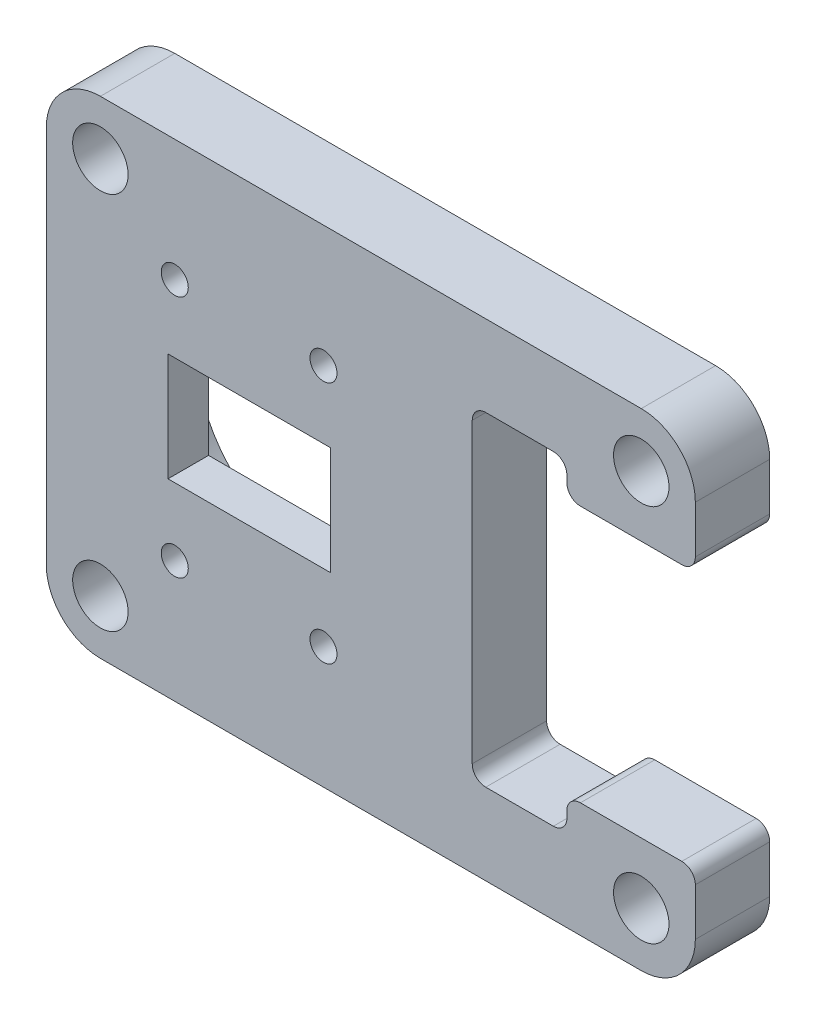
SolidWorks part; units mm, degrees
ref_plane "Front Plane" through (0, 0, 0) normal (0, 0, 1) x (1, 0, 0)
ref_plane "Top Plane" through (0, 0, 0) normal (0, 1, 0) x (1, 0, 0)
ref_plane "Right Plane" through (0, 0, 0) normal (1, 0, 0) x (0, 0, -1)
sketch "Sketch1" plane through (0, 0, 0) normal (0, 0, 1) x (1, 0, 0)
  line L1 (-20, -18) -> (20, -18)
  line L2 (-24, -14) -> (-24, 14)
  line L3 (-20, 18) -> (20, 18)
  line L4 (24, -14) -> (24, 14)
  line L5 (-24, -18) -> (24, 18) construction
  line L6 (-24, 18) -> (24, -18) construction
  arc A0 (-24, -14) -> (-20, -18) centre (-20, -14) ccw
  arc A1 (20, -18) -> (24, -14) centre (20, -14) ccw
  arc A2 (24, 14) -> (20, 18) centre (20, 14) ccw
  arc A3 (-20, 18) -> (-24, 14) centre (-20, 14) ccw
  circle A4 centre (-20, -14) radius 2.05
  circle A5 centre (-20, 14) radius 2.05
  circle A6 centre (20, 14) radius 2.05
  circle A7 centre (20, -14) radius 2.05
  point P0 (0, 0)
  dimension "D3" = 4
  dimension "D4" = 4
  dimension "D5" = 4
  dimension "D6" = 4
  dimension "D7" = 4.1
  dimension "D8" = 4.1
  dimension "D9" = 4.1
  dimension "D10" = 4.1
  dimension "D1" = 48
  dimension "D2" = 36
extrude "Boss-Extrude1" add sketch "Sketch1" along normal mid plane 5.5
sketch "Sketch2" plane through (0, 0, -2.75) normal (0, 0, 1) x (1, 0, 0)
  line L0 (-1000, 0) -> (49000, 0) construction
  line L1 (-9, -1000) -> (-9, 49000) construction
  circle A0 centre (-20, -14) radius 2.05 construction
  circle A1 centre (-9, 0) radius 9.5
  dimension "D2" = 19
  dimension "D1" = 11
extrude "Cut-Extrude1" cut sketch "Sketch2" along normal blind 2.5
sketch "Sketch3" plane through (0, 0, -0.25) normal (0, 0, -1) x (1, 0, 0)
  line L1 (-15, -4) -> (-3, -4)
  line L2 (-15, -4) -> (-15, 4)
  line L3 (-15, 4) -> (-3, 4)
  line L4 (-3, -4) -> (-3, 4)
  line L5 (-15, -4) -> (-3, 4) construction
  line L6 (-15, 4) -> (-3, -4) construction
  point P0 (-9, 0)
  dimension "D1" = 12
  dimension "D2" = 8
extrude "Cut-Extrude2" cut sketch "Sketch3" against normal through all
sketch "Sketch4" plane through (0, 0, 2.75) normal (0, 0, 1) x (1, 0, 0)
  line L0 (-1003, 0) -> (48997, 0) construction
  line L1 (-3, 4) -> (-3, -4) construction
  line L2 (-9, -996) -> (-9, 49004) construction
  line L3 (-15, 4) -> (-3, 4) construction
  line L5 (-3.5, -9) -> (-14.5, -9) construction
  line L6 (-3.5, -9) -> (-3.5, 9) construction
  line L7 (-3.5, 9) -> (-14.5, 9) construction
  line L8 (-14.5, -9) -> (-14.5, 9) construction
  line L9 (-3.5, -9) -> (-14.5, 9) construction
  line L10 (-3.5, 9) -> (-14.5, -9) construction
  circle A0 centre (-14.5, 9) radius 1
  circle A1 centre (-3.5, 9) radius 1
  circle A2 centre (-3.5, -9) radius 1
  circle A3 centre (-14.5, -9) radius 1
  point P5 (-3, 0)
  point P6 (-9, 0)
  point P10 (-9, 4)
  dimension "D3" = 2
  dimension "D4" = 2
  dimension "D5" = 2
  dimension "D6" = 2
  dimension "D1" = 11
  dimension "D2" = 18
extrude "Cut-Extrude3" cut sketch "Sketch4" against normal through all
sketch "Sketch5" plane through (0, 0, 2.75) normal (0, 0, 1) x (1, 0, 0)
  line L0 (-1000, 0) -> (49000, 0) construction
  line L1 (-15, 4) -> (-3, 4) construction
  line L2 (7.5, -12) -> (14.5, -12)
  line L3 (7.5, -12) -> (7.5, 12)
  line L4 (7.5, 12) -> (14.5, 12)
  line L5 (14.5, -12) -> (14.5, 12)
  line L6 (7.5, -12) -> (14.5, 12) construction
  line L7 (7.5, 12) -> (14.5, -12) construction
  point P1 (11, 0)
  point P8 (-9, 4)
  dimension "D1" = 7
  dimension "D2" = 24
  dimension "D3" = 20
extrude "Cut-Extrude4" cut sketch "Sketch5" against normal through all
sketch "Sketch6" plane through (0, 0, -2.75) normal (0, 0, -1) x (-1, 0, 0)
  line L0 (-24, -14) -> (-24, 14) construction
  line L1 (-36.5, 9.5) -> (-11.5, 9.5)
  line L2 (-36.5, 9.5) -> (-36.5, -9.5)
  line L3 (-36.5, -9.5) -> (-11.5, -9.5)
  line L4 (-11.5, 9.5) -> (-11.5, -9.5)
  line L5 (-36.5, 9.5) -> (-11.5, -9.5) construction
  line L6 (-36.5, -9.5) -> (-11.5, 9.5) construction
  point P0 (-24, 0)
  dimension "D1" = 19
  dimension "D2" = 25
extrude "Cut-Extrude5" cut sketch "Sketch6" against normal through all
fillet "Fillet1" radius 1 8 edges at (14.5, -12, 0) (7.5, -12, 0) (7.5, 12, 0) (14.5, 12, 0) (14.5, 9.5, 0) (24, 9.5, 0) (24, -9.5, 0) (14.5, -9.5, 0)
